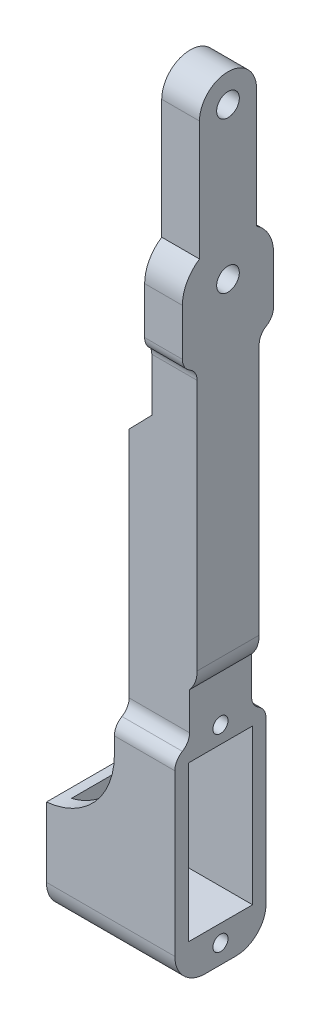
SolidWorks part; units mm, degrees
ref_plane "前视基准面" through (0, 0, 0) normal (0, 0, 1) x (1, 0, 0)
ref_plane "上视基准面" through (0, 0, 0) normal (0, 1, 0) x (1, 0, 0)
ref_plane "右视基准面" through (0, 0, 0) normal (1, 0, 0) x (0, 0, -1)
sketch "Sketch1" plane through (0, 0, 0) normal (1, 0, 0) x (0, 0, -1)
  circle A0 centre (2.9834, 10.8268) radius 7.75 construction
  circle A1 centre (2.9834, 10.8268) radius 6.25 construction
  circle A2 centre (2.9834, 18.5768) radius 0.8
  circle A3 centre (2.9834, 3.0768) radius 0.8
  circle A4 centre (-3.2666, 10.8268) radius 0.8
  circle A5 centre (9.2334, 10.8268) radius 0.8
  circle A6 centre (2.9834, 10.8268) radius 10
  circle A7 centre (2.9834, 10.8268) radius 3.3018
  dimension "D1" = 15.5
  dimension "D2" = 12.5
  dimension "D3" = 20
extrude "Boss-Extrude1" add sketch "Sketch1" along normal blind 1.5
sketch "Sketch2" plane through (0, 0, 0) normal (-1, 0, 0) x (0, 0, 1)
  line L0 (-2.9834, 10.8268) -> (-2.9834, 25.4318) construction
  line L2 (-12.9834, 90.8268) -> (7.0166, 90.8268) construction
  line L3 (-12.9834, 90.8268) -> (-12.9834, 10.8268) construction
  line L4 (-12.9834, 10.8268) -> (7.0166, 10.8268) construction
  line L5 (7.0166, 90.8268) -> (7.0166, 10.8268) construction
  line L6 (-12.9834, 90.8268) -> (7.0166, 10.8268) construction
  line L7 (-12.9834, 10.8268) -> (7.0166, 90.8268) construction
  line L8 (-15.5319, 90.8268) -> (9.5652, 90.8268)
  line L9 (-15.5319, 90.8268) -> (-15.5319, 10.8268)
  line L10 (-15.5319, 10.8268) -> (9.5652, 10.8268) construction
  line L11 (9.5652, 90.8268) -> (9.5652, 10.8268)
  line L12 (-15.5319, 90.8268) -> (9.5652, 10.8268) construction
  line L13 (-15.5319, 10.8268) -> (9.5652, 90.8268) construction
  circle A0 centre (-2.9834, 10.8268) radius 10 construction
  arc A1 (-12.9834, 10.8268) -> (7.0166, 10.8268) centre (-2.9834, 10.8268) cw construction
  circle A2 centre (-2.9834, 10.8268) radius 12.5485 construction
  circle A3 centre (-2.9834, 10.8268) radius 10
  arc A4 (-15.5319, 10.8268) -> (9.5652, 10.8268) centre (-2.9834, 10.8268) ccw
  circle A5 centre (-2.9834, 10.8268) radius 0.6321 construction
  point P1 (-2.9834, 50.8268)
  point P12 (-2.9834, 50.8268)
  dimension "D1" = 0
  dimension "D2" = 80
extrude "Boss-Extrude2" add sketch "Sketch2" against normal blind 9
sketch "Sketch3" plane through (9, 0, 0) normal (1, 0, 0) x (0, 0, -1)
  line L0 (2.9834, 95.8916) -> (2.9834, 22.8694) construction
  line L1 (-9.5652, 90.8268) -> (15.5319, 90.8268) construction
  line L3 (-3.0511, 36.1504) -> (-3.0511, 97.5726)
  line L4 (-3.0511, 97.5726) -> (-16.389, 97.5726)
  line L5 (-16.389, 97.5726) -> (-16.389, 8.1411)
  line L6 (-16.389, 8.1411) -> (-9.5652, 10.8268)
  line L7 (22.3558, 8.1411) -> (15.5319, 10.8268)
  line L8 (22.3558, 97.5726) -> (22.3558, 8.1411)
  line L9 (9.0179, 97.5726) -> (22.3558, 97.5726)
  line L10 (9.0179, 36.1504) -> (9.0179, 97.5726)
  circle A0 centre (2.9834, 85.8268) radius 1.5
  spline S0 degree 3 poles (-9.5652, 10.8268) (-9.6442, 15.1222) (-6.9162, 23.507) (-3.4283, 31.5617) (-3.0511, 36.1504) knots 0 0 0 0 0.482385 1 1 1 1
  spline S1 degree 3 poles (15.5319, 10.8268) (15.611, 15.1222) (12.883, 23.507) (9.395, 31.5617) (9.0179, 36.1504) knots 0 0 0 0 0.482385 1 1 1 1
  dimension "D1" = 5
extrude "Cut-Extrude1" cut sketch "Sketch3" against normal through all both and the other way through all
fillet "Fillet1" radius 5 2 edges at (4.5, 90.8268, -9.0179) (4.5, 90.8268, 3.0511)
sketch "Sketch4" plane through (9, 0, 0) normal (1, 0, 0) x (0, 0, -1)
  line L0 (2.9834, 85.8268) -> (2.9834, 105.8268) construction
  line L1 (-0.7887, 85.8268) -> (-0.7887, 105.8268)
  line L2 (6.7554, 85.8268) -> (6.7554, 105.8268)
  arc A0 (-0.7887, 85.8268) -> (6.7554, 85.8268) centre (2.9834, 85.8268) ccw
  arc A1 (6.7554, 105.8268) -> (-0.7887, 105.8268) centre (2.9834, 105.8268) ccw
  circle A2 centre (2.9834, 105.8268) radius 1.5
  circle A3 centre (2.9834, 85.8268) radius 1.5
  point P3 (2.9834, 95.8268)
  dimension "D1" = 20
extrude "Boss-Extrude3" add sketch "Sketch4" against normal blind 5
sketch "Sketch5" plane through (0, 0, 0) normal (-1, 0, 0) x (0, 0, 1)
  line L0 (3.0511, 66.6904) -> (-0.5206, 90.6184)
  line L1 (3.0511, 36.1504) -> (3.0511, 85.8268) construction
  line L2 (-0.5206, 90.6184) -> (8.9944, 90.6184)
  line L3 (8.9944, 90.6184) -> (4.4528, 66.6904)
  line L4 (4.4528, 66.6904) -> (3.0511, 66.6904)
  line L5 (-9.0179, 66.6904) -> (-5.4462, 90.6184)
  line L6 (-9.0179, 85.8268) -> (-9.0179, 36.1504) construction
  line L7 (-5.4462, 90.6184) -> (-12.4698, 95.2806)
  line L8 (-12.4698, 95.2806) -> (-31.4476, 66.6904)
  line L9 (-31.4476, 66.6904) -> (-9.0179, 66.6904)
  arc A0 (0.7887, 90.0108) -> (-1.9489, 90.8268) centre (-1.9489, 85.8268) ccw construction
  arc A1 (-4.0179, 90.8268) -> (-6.7554, 90.0108) centre (-4.0179, 85.8268) ccw construction
  dimension "D1" = 0
extrude "Cut-Extrude2" cut sketch "Sketch5" against normal up to surface (4 mm away) up to face at (4, 96.25, -2.9834)
fillet "Fillet3" radius 2 2 edges at (2, 90.6184, -5.4462) (2, 90.6184, -0.5206)
sketch "Sketch6" plane through (9, 0, 0) normal (1, 0, 0) x (0, 0, -1)
  line L0 (9.0179, 36.1504) -> (9.0179, 28.2815) construction
  line L2 (-3.0511, 36.1504) -> (9.0179, 36.1504)
  line L3 (-3.0511, 36.1504) -> (-3.0511, 0)
  line L4 (-3.0511, 0) -> (9.0179, 0)
  line L5 (9.0179, 36.1504) -> (9.0179, 0)
extrude "Boss-Extrude4" add sketch "Sketch6" against normal up to surface (9 mm away) up to face at (0, 85.8268, -4.4834)
sketch "Sketch7" plane through (9, 0, 0) normal (1, 0, 0) x (0, 0, -1)
  line L0 (-3.0511, 36.1504) -> (-3.0511, -1.9848) construction
  line L1 (-3.0511, -1.9848) -> (-23.4996, -1.9848)
  line L2 (-23.4996, -1.9848) -> (-3.0511, 36.1504)
  line L3 (9.0179, 36.1504) -> (9.0179, -7.6597) construction
  line L4 (9.0179, -7.6597) -> (33.092, 2.7443)
  line L5 (33.092, 2.7443) -> (9.0179, 36.1504)
  line L6 (-3.0511, 36.1504) -> (-3.0511, 6.6932)
  line L7 (-3.0511, 6.6932) -> (9.0179, 6.6932)
  line L8 (9.0179, 6.6932) -> (9.0179, 36.1504)
  line L9 (-3.0511, -1.9848) -> (9.0179, -7.6597)
extrude "Cut-Extrude3" cut sketch "Sketch7" against normal through all both and the other way through all
sketch "Sketch8" plane through (9, 0, 0) normal (1, 0, 0) x (0, 0, -1)
  line L0 (2.9834, 88.9737) -> (2.9834, 82.9384) construction
  line L2 (7.2334, 31.9739) -> (-1.2666, 31.9739)
  line L3 (7.2334, 31.9739) -> (7.2334, 11.4739)
  line L4 (7.2334, 11.4739) -> (-1.2666, 11.4739)
  line L5 (-1.2666, 31.9739) -> (-1.2666, 11.4739)
  line L6 (7.2334, 31.9739) -> (-1.2666, 11.4739) construction
  line L7 (7.2334, 11.4739) -> (-1.2666, 31.9739) construction
  line L8 (3.7847, 34.2239) -> (2.1821, 34.2239) construction
  line L9 (3.7847, 34.2239) -> (3.7847, 9.2239) construction
  line L10 (3.7847, 9.2239) -> (2.1821, 9.2239) construction
  line L11 (2.1821, 34.2239) -> (2.1821, 9.2239) construction
  line L12 (3.7847, 34.2239) -> (2.1821, 9.2239) construction
  line L13 (3.7847, 9.2239) -> (2.1821, 34.2239) construction
  circle A0 centre (2.9834, 34.2239) radius 1
  circle A1 centre (2.9834, 9.2239) radius 1
  circle A2 centre (2.9834, 85.8268) radius 0.5708 construction
  point P1 (2.9834, 21.7239)
  point P8 (2.9834, 21.7239)
  point P18 (2.9834, 19.6932)
  point P19 (2.9834, 22.2332)
  point P20 (2.9834, 21.7239)
  dimension "D1" = 8.5
  dimension "D2" = 20.5
  dimension "D3" = 25
  dimension "D5" = 0
  dimension "D6" = 0
extrude "Cut-Extrude4" cut sketch "Sketch8" against normal through all both and the other way through all
fillet "Fillet4" radius 4 2 edges at (4.5, 6.6932, -9.0179) (4.5, 6.6932, 3.0511)
sketch "Sketch9" plane through (9, 0, 0) normal (1, 0, 0) x (0, 0, -1)
  line L1 (-8.9789, -0.9142) -> (15.4035, -0.9142)
  line L2 (-8.9789, -0.9142) -> (-8.9789, 40.2965)
  line L3 (-8.9789, 40.2965) -> (15.4035, 40.2965)
  line L4 (15.4035, -0.9142) -> (15.4035, 40.2965)
extrude "Cut-Extrude5" cut sketch "Sketch9" against normal blind 1
fillet "Fillet5" radius 4 1 edges at (9, 40.2965, -2.9834)
sketch "Sketch10" plane through (0, 0, 0) normal (-1, 0, 0) x (0, 0, 1)
  circle A0 centre (-2.9834, 85.8268) radius 20.0653
extrude "Cut-Extrude6" cut sketch "Sketch10" against normal blind 3
sketch "Sketch11" plane through (0, 0, 0) normal (-1, 0, 0) x (0, 0, 1)
  line L0 (-3.0031, 100.8499) -> (-3.0031, 107.7727) construction
  line L1 (-9.0179, 76.2586) -> (-9.0179, 35.3573) construction
  line L2 (-7.11, 76.2586) -> (-7.11, 35.3573)
  line L3 (-10.9258, 76.2586) -> (-10.9258, 35.3573)
  line L4 (-9.0179, 66.6904) -> (-9.0179, 10.6932) construction
  line L5 (-9.0179, 66.6904) -> (-9.0179, 85.8268) construction
  line L6 (3.0116, 76.2586) -> (3.0116, 35.3573) construction
  line L7 (1.1037, 76.2586) -> (1.1037, 35.3573)
  line L8 (4.9195, 76.2586) -> (4.9195, 35.3573)
  arc A0 (-7.11, 76.2586) -> (-10.9258, 76.2586) centre (-9.0179, 76.2586) ccw
  arc A1 (-10.9258, 35.3573) -> (-7.11, 35.3573) centre (-9.0179, 35.3573) ccw
  arc A2 (1.1037, 76.2586) -> (4.9195, 76.2586) centre (3.0116, 76.2586) cw
  arc A3 (4.9195, 35.3573) -> (1.1037, 35.3573) centre (3.0116, 35.3573) cw
  point P5 (-9.0179, 55.8079)
  point P19 (3.0116, 55.8079)
extrude "Cut-Extrude7" cut sketch "Sketch11" against normal through all both and the other way through all
fillet "Fillet6" radius 2 4 edges at (4, 33.4494, -9.0179) (4, 33.4498, 3.0511) (6.5, 78.1665, -9.0179) (6.5, 78.1661, 3.0511)
chamfer "Chamfer1" distance 3 angle 45 1 edges at (3, 65.7614, -3.0035)
sketch "Sketch12" plane through (0, 0, 0) normal (-1, 0, 0) x (0, 0, 1)
  line L0 (-2.9834, 9.2239) -> (-2.9834, 16.2239) construction
  line L1 (-5.0179, 6.6932) -> (-0.9489, 6.6932) construction
  line L2 (-5.0179, 6.6932) -> (-0.9489, 6.6932)
  line L3 (-9.0179, 10.6932) -> (-9.0179, 19.8959)
  line L4 (-9.0179, 32) -> (-9.0179, 10.6932) construction
  line L5 (-9.0179, 19.8959) -> (3.0511, 19.8959)
  line L6 (3.0511, 10.6932) -> (3.0511, 31.9768) construction
  line L7 (3.0511, 19.8959) -> (3.0511, 10.6932)
  circle A0 centre (-2.9834, 16.2239) radius 1
  arc A1 (-0.9489, 6.6932) -> (3.0511, 10.6932) centre (-0.9489, 10.6932) ccw construction
  arc A2 (-0.9489, 6.6932) -> (3.0511, 10.6932) centre (-0.9489, 10.6932) ccw
  circle A3 centre (-2.9834, 9.2239) radius 1 construction
  circle A4 centre (-2.9834, 9.2239) radius 1
  arc A5 (-9.0179, 10.6932) -> (-5.0179, 6.6932) centre (-5.0179, 10.6932) ccw construction
  arc A6 (-9.0179, 10.6932) -> (-5.0179, 6.6932) centre (-5.0179, 10.6932) ccw
  dimension "D1" = 7
extrude "Boss-Extrude5" add sketch "Sketch12" along normal blind 9
sketch "Sketch14" plane through (0, 0, 0) normal (1, 0, 0) x (0, 0, -1)
  line L0 (-1.2666, 19.8959) -> (7.2334, 19.8959) construction
  line L1 (7.2334, 19.8959) -> (-1.2666, 19.8959)
  line L2 (7.2334, 19.8959) -> (7.2334, 11.4739)
  line L3 (7.2334, 11.4739) -> (-1.2666, 11.4739)
  line L4 (-1.2666, 19.8959) -> (-1.2666, 11.4739)
  line L5 (7.2334, 11.4739) -> (7.2334, 19.8959) construction
  line L6 (-1.2666, 31.9739) -> (-1.2666, 11.4739) construction
  line L7 (-1.2666, 19.8959) -> (-1.2666, 11.4739) construction
extrude "Cut-Extrude8" cut sketch "Sketch14" against normal offset from surface (7.5 mm away) 1.5 up to face at (-9, 16.2239, -1.9834)
fillet "Fillet7" radius 10 1 edges at (0, 19.8959, 2.1589)
